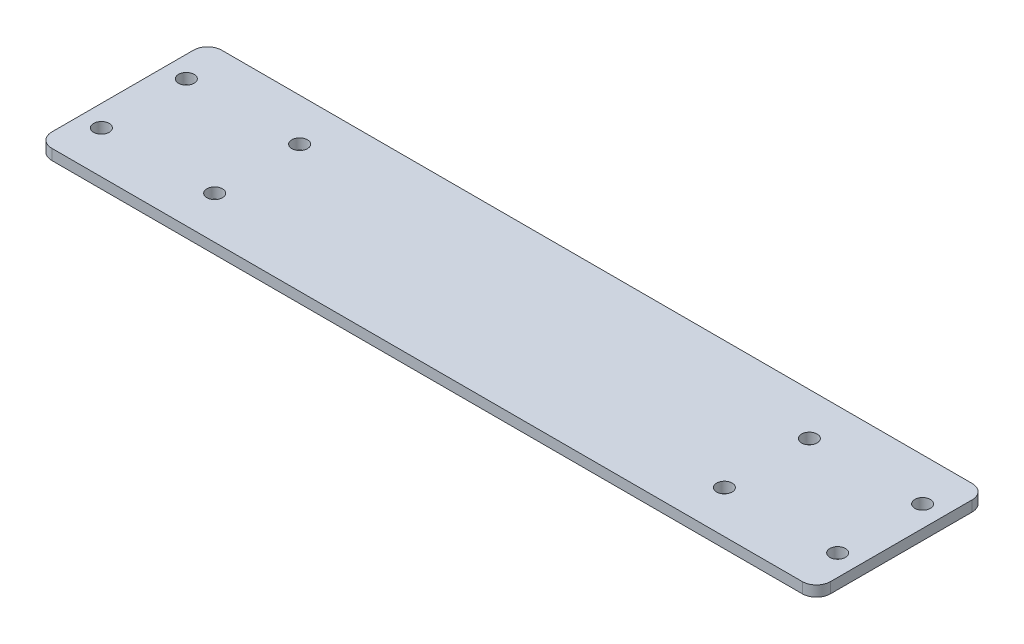
SolidWorks part; units mm, degrees
note: The reader was unsure of these and kept them because the rebuilt part matched: thickness of "Base-Flange1", "Sheet-Metal4".
material "ASTM A36 Steel"
ref_plane "Front Plane" through (0, 0, 0) normal (0, 0, 1) x (1, 0, 0)
ref_plane "Top Plane" through (0, 0, 0) normal (0, 1, 0) x (1, 0, 0)
ref_plane "Right Plane" through (0, 0, 0) normal (1, 0, 0) x (0, 0, -1)
sketch "Sketch1" plane through (0, 0, 0) normal (0, 1, 0) x (1, 0, 0)
  line L0 (-55, 0) -> (55, 0) construction
  line L1 (-349.25, -76.2) -> (349.25, -76.2)
  line L2 (-349.25, -76.2) -> (-349.25, 76.2)
  line L3 (-349.25, 76.2) -> (349.25, 76.2)
  line L4 (349.25, -76.2) -> (349.25, 76.2)
  line L5 (-349.25, -76.2) -> (349.25, 76.2) construction
  line L6 (-349.25, 76.2) -> (349.25, -76.2) construction
  line L7 (0, -55) -> (0, 55) construction
  circle A0 centre (228.6, 38.1) radius 6.985
  circle A1 centre (330.2, 38.1) radius 6.985
  circle A2 centre (330.2, -38.1) radius 6.985
  circle A3 centre (228.6, -38.1) radius 6.985
  circle A4 centre (-228.6, -38.1) radius 6.985
  circle A5 centre (-330.2, -38.1) radius 6.985
  circle A6 centre (-330.2, 38.1) radius 6.985
  circle A7 centre (-228.6, 38.1) radius 6.985
  point P0 (0, 0)
  dimension "D3" = 13.97
  dimension "D5" = 101.6
  dimension "D1" = 152.4
  dimension "D2" = 698.5
  dimension "D4" = 38.1
  dimension "D6" = 660.4
base flange "Base-Flange1" sketch "Sketch1" thickness 9.525 reverse thickness direction no parameters "D1"=6.3754
fillet "Fillet1" radius 12.7 4 edges at (349.25, -4.7625, -76.2) (-349.25, -4.7625, -76.2) (-349.25, -4.7625, 76.2) (349.25, -4.7625, 76.2)
sketch "Bend-Lines1" [suppressed] plane through (0, 0, 0) normal (0, 1, 0) x (1, 0, 0)
sketch "Bounding-Box1" [suppressed] plane through (0, 0, 0) normal (0, 1, 0) x (1, 0, 0)
sheet metal parameters "Sheet-Metal4" thickness 9.525 parameters "D1"=6.3754, "D7"=6.35
flat pattern "Flat-Pattern4" [suppressed]
sketch "Bend-Lines2" plane through (0, 0, 0) normal (0, 1, 0) x (1, 0, 0)
sketch3d "Bounding-Box2" [suppressed]
  line L0 (-349.25, 76.2, 0) -> (349.25, 76.2, 0) construction
  line L1 (-349.25, -76.2, 0) -> (349.25, -76.2, 0) construction
  line L2 (-349.25, 76.2, 0) -> (-349.25, -76.2, 0) construction
  line L3 (349.25, 76.2, 0) -> (349.25, -76.2, 0) construction
equation "\"PRIMER_USAGE\"= ( \"SW-SurfaceArea\" / 144 ) / 135"
equation "\"WET_PAINT_USAGE\"= ( \"SW-SurfaceArea\" / 144 ) / 125"
equation "\"POWDERCOAT_USAGE\"= ( \"SW-SurfaceArea\" / 144 ) / 29.79"
equation "\"DECKOVER_USAGE\"= ( \"SW-SurfaceArea\" / 144 ) / 75"
equation "\"SW_NON-SKID\"= ( \"SW-SurfaceArea\" / 144 ) / 165"
equation "\"TYPE_1_ANODIZATING\"= ( \"SW-SurfaceArea\" * 0.0001 )"
equation "\"TYPE_2_ANODIZING\"= ( \"SW-SurfaceArea\" * 0.0005 )"
equation "\"TYPE_3_ANODIZING-HARDCOAT\"= ( \"SW-SurfaceArea\" * 0.003 )"
